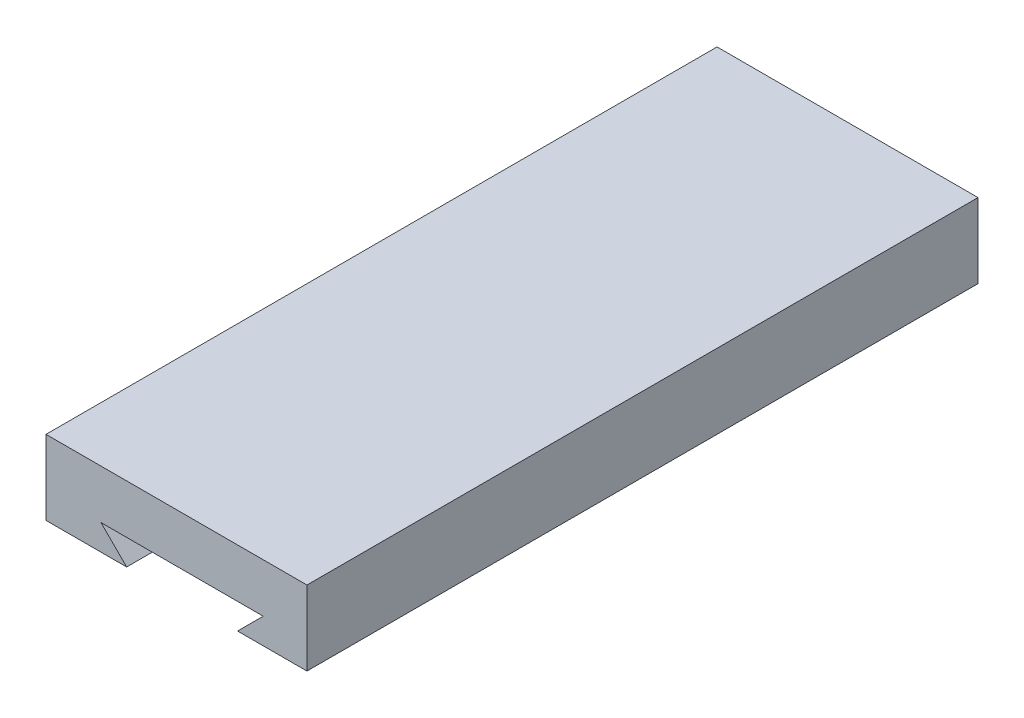
SolidWorks part; units mm, degrees
ref_plane "Front Plane" through (0, 0, 0) normal (0, 0, 1) x (1, 0, 0)
ref_plane "Top Plane" through (0, 0, 0) normal (0, 1, 0) x (1, 0, 0)
ref_plane "Right Plane" through (0, 0, 0) normal (1, 0, 0) x (0, 0, -1)
sketch "Sketch1" plane through (0, 0, 0) normal (0, 0, 1) x (1, 0, 0)
  line L1 (-41.0211, 23.825) -> (28.9789, 23.825)
  line L2 (-41.0211, 23.825) -> (-41.0211, 3.825)
  line L3 (-41.0211, 3.825) -> (28.9789, 3.825)
  line L4 (28.9789, 23.825) -> (28.9789, 3.825)
  dimension "D1" = 70
  dimension "D2" = 20
extrude "Boss-Extrude1" add sketch "Sketch1" along normal blind 180
sketch "Sketch2" plane through (0, 0, 180) normal (0, 0, 1) x (1, 0, 0)
  line L0 (-19.3869, 3.825) -> (-26.2668, 10.7049)
  line L1 (-41.0211, 3.825) -> (28.9789, 3.825) construction
  line L2 (-26.2668, 10.7049) -> (17.2407, 10.7049)
  line L3 (17.2407, 10.7049) -> (10.3608, 3.825)
  line L4 (-19.3869, 3.825) -> (10.3608, 3.825)
  dimension "D1" = 45
  dimension "D2" = 45
extrude "Cut-Extrude1" cut sketch "Sketch2" against normal blind 180 and the other way through all
